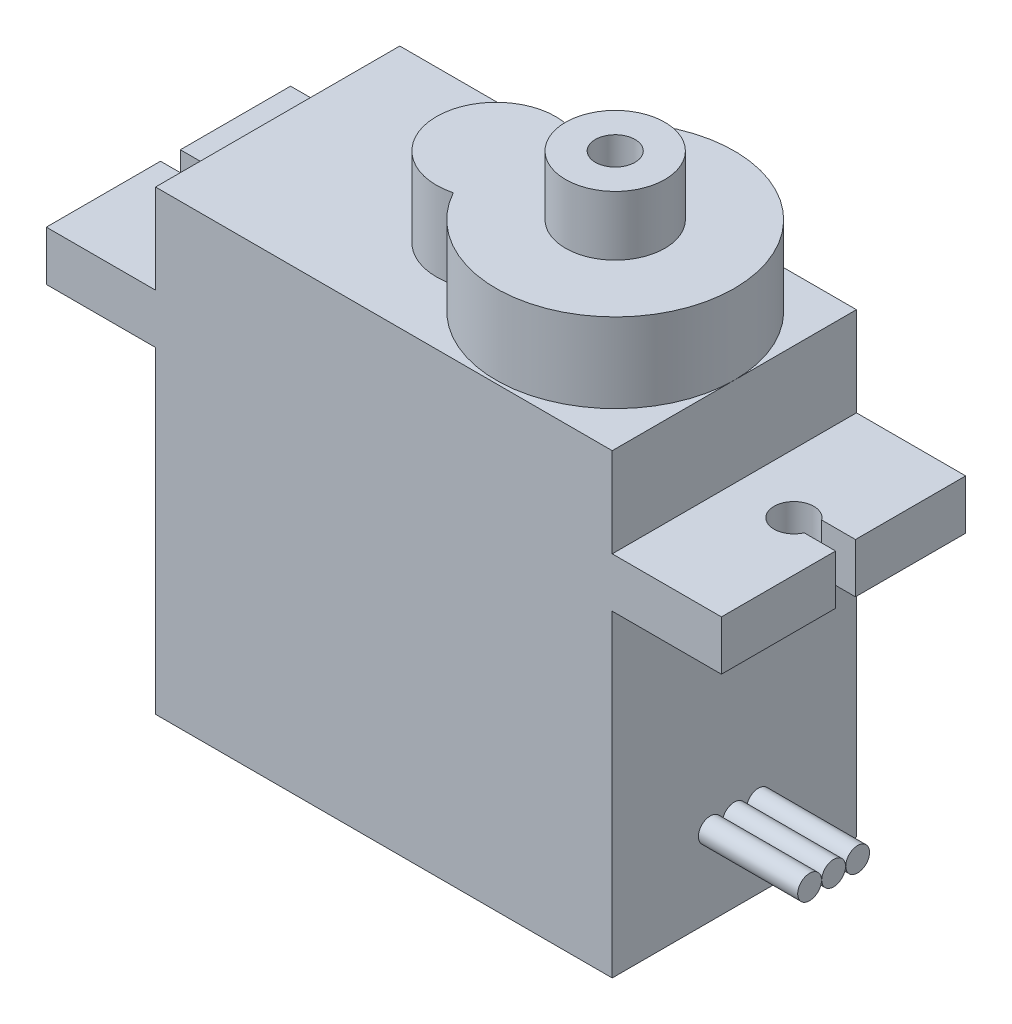
SolidWorks part; units mm, degrees
ref_plane "Front Plane" through (0, 0, 0) normal (0, 0, 1) x (1, 0, 0)
ref_plane "Top Plane" through (0, 0, 0) normal (0, 1, 0) x (1, 0, 0)
ref_plane "Right Plane" through (0, 0, 0) normal (1, 0, 0) x (0, 0, -1)
sketch "Sketch1" plane through (0, 0, 0) normal (0, 1, 0) x (1, 0, 0)
  line L1 (-11.5, -6.15) -> (11.5, -6.15)
  line L2 (-11.5, -6.15) -> (-11.5, 6.15)
  line L3 (-11.5, 6.15) -> (11.5, 6.15)
  line L4 (11.5, -6.15) -> (11.5, 6.15)
  line L5 (-11.5, -6.15) -> (11.5, 6.15) construction
  line L6 (-11.5, 6.15) -> (11.5, -6.15) construction
  point P0 (0, 0)
  dimension "D1" = 12.3
  dimension "D2" = 23
extrude "Boss-Extrude1" add sketch "Sketch1" along normal blind 23
sketch "Sketch2" plane through (-11.5, 0, 0) normal (-1, 0, 0) x (0, 0, 1)
  line L0 (-6.15, 23) -> (-6.15, 0) construction
  line L1 (-6.15, 18.5) -> (6.15, 18.5)
  line L2 (-6.15, 18.5) -> (-6.15, 16)
  line L3 (-6.15, 16) -> (6.15, 16)
  line L4 (6.15, 18.5) -> (6.15, 16)
  line L5 (6.15, 23) -> (6.15, 0) construction
  line L6 (-6.15, 0) -> (6.15, 0) construction
  dimension "D1" = 16
  dimension "D2" = 2.5
extrude "Boss-Extrude2" add sketch "Sketch2" along normal blind 5.5
sketch "Sketch3" plane through (0, 18.5, 0) normal (0, 1, 0) x (1, 0, 0)
  line L0 (-17, -6.15) -> (-17, 6.15) construction
  line L1 (-17, 0.6) -> (-15.3, 0.6)
  line L2 (-17, 0.6) -> (-17, -0.4)
  line L4 (-17, -0.4) -> (-15.4165, -0.4)
  line L6 (-11.5, -6.15) -> (-11.5, 6.15) construction
  arc A0 (-15.4165, -0.4) -> (-15.3, 0.6) centre (-14.5, 0) ccw
  point P4 (0, 0)
  point P7 (-15.5448, 1.6902)
  point P10 (-11.5, 0)
  point P11 (0, 0)
  point P12 (0, 0)
  point P15 (0, 0)
  dimension "D1" = 2.5
  dimension "D2" = 2
  dimension "D3" = 1
extrude "Cut-Extrude1" cut sketch "Sketch3" against normal blind 5
mirror "Mirror1" about plane through (0, 0, 0) normal (1, 0, 0) of "Cut-Extrude1", "Boss-Extrude2"
sketch "Sketch4" plane through (0, 23, 0) normal (0, 1, 0) x (1, 0, 0)
  line L1 (11.5, -6.15) -> (11.5, 6.15) construction
  arc A0 (0.25, -2.9047) -> (0.25, 2.9047) centre (5.5, 0) ccw
  arc A1 (0.25, 2.9047) -> (0.25, -2.9047) centre (-0.5, 0) ccw
  point P6 (0, 0)
  dimension "D1" = 12
  dimension "D3" = 6
  dimension "D4" = 6
  dimension "D2" = 6
extrude "Boss-Extrude3" add sketch "Sketch4" along normal blind 4
sketch "Sketch5" plane through (0, 27, 0) normal (0, 1, 0) x (1, 0, 0)
  circle A0 centre (5.5, 0) radius 2.5
  circle A1 centre (5.5, 0) radius 6 construction
  circle A2 centre (5.5, 0) radius 1
  point P6 (0, 0)
  dimension "D1" = 0
  dimension "D2" = 5
  dimension "D3" = 2
extrude "Boss-Extrude4" add sketch "Sketch5" along normal blind 3
sketch "Sketch7" plane through (11.5, 0, 0) normal (1, 0, 0) x (0, 0, -1)
  line L0 (-6.15, 0) -> (6.15, 0) construction
  circle A0 centre (0, 4) radius 0.6
  circle A1 centre (1.21, 4) radius 0.6
  circle A2 centre (-1.21, 4) radius 0.6
  point P6 (0, 0)
  point P10 (0, 0)
  dimension "D1" = 1.2
  dimension "D2" = 1.2
  dimension "D3" = 1.2
  dimension "D4" = 4
  dimension "D5" = 1.21
  dimension "D6" = 1.21
extrude "Boss-Extrude8" add sketch "Sketch7" along normal blind 5
